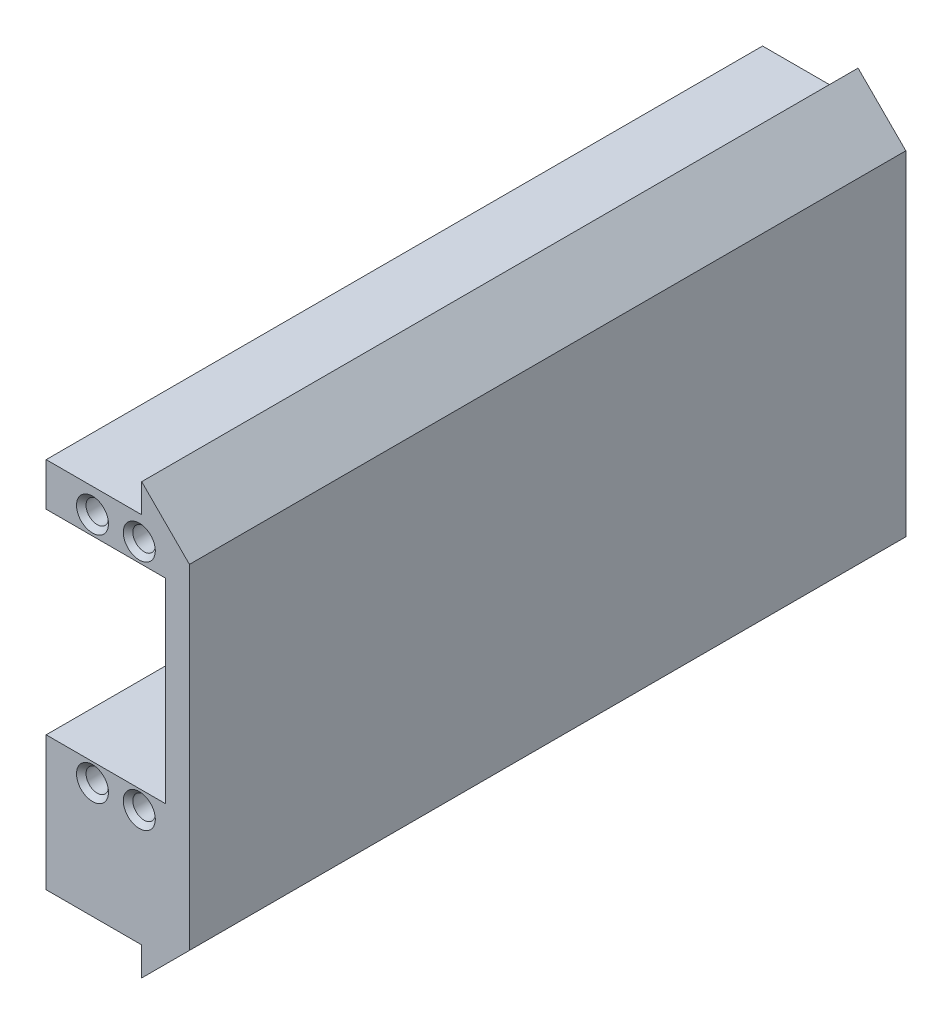
SolidWorks part; units mm, degrees
material "ABS"
ref_plane "Front Plane" through (0, 0, 0) normal (0, 0, 1) x (1, 0, 0)
ref_plane "Top Plane" through (0, 0, 0) normal (0, 1, 0) x (1, 0, 0)
ref_plane "Right Plane" through (0, 0, 0) normal (1, 0, 0) x (0, 0, -1)
sketch "Sketch1" plane through (0, 0, 0) normal (0, 0, 1) x (1, 0, 0)
  line L0 (-15, 45) -> (15, 45)
  line L1 (-15, 45) -> (15, 45) construction
  line L2 (-15, 45) -> (-15, -45) construction
  line L3 (-15, -45) -> (15, -45) construction
  line L4 (15, 45) -> (15, -45) construction
  line L5 (-15, 45) -> (15, -45) construction
  line L6 (-15, -45) -> (15, 45) construction
  line L7 (15, 45) -> (15, -45)
  line L8 (15, -45) -> (-15, -45)
  line L9 (-15, -45) -> (-15, -10.9)
  line L10 (-15, -10.9) -> (10, -10.9)
  line L11 (10, -10.9) -> (10, 30)
  line L12 (10, 30) -> (-15, 30)
  line L13 (-15, 30) -> (-15, 45)
  point P0 (0, 0)
  dimension "D1" = 90
  dimension "D2" = 30
  dimension "D3" = 40.9
  dimension "D4" = 15
  dimension "D5" = 5
extrude "Boss-Extrude1" add sketch "Sketch1" along normal blind 150
sketch "Sketch2" plane through (0, 0, 150) normal (0, 0, 1) x (1, 0, 0)
  line L0 (10, 30) -> (-10.8, 30) construction
  line L1 (-15, 30) -> (10, 30) construction
  line L2 (-0.4, 30) -> (-0.4, 33.89) construction
  line L3 (-0.4, 33.89) -> (4.5, 33.89) construction
  line L4 (10, 30) -> (10, -10.9) construction
  line L5 (10, 9.55) -> (15, 9.55) construction
  line L7 (15, -45) -> (15, 45) construction
  circle A0 centre (4.5, 33.89) radius 2.35
  circle A1 centre (-5.3, 33.89) radius 2.35
  circle A4 centre (4.5, -14.79) radius 2.35
  circle A5 centre (-5.3, -14.79) radius 2.35
  dimension "D4" = 4.7
  dimension "D1" = 20.8
  dimension "D2" = 3.89
  dimension "D3" = 4.9
extrude "Cut-Extrude1" cut sketch "Sketch2" against normal blind 8
sketch "Sketch3" plane through (0, 0, 0) normal (0, 0, -1) x (-1, 0, 0)
  line L0 (-10, 30) -> (10.8, 30) construction
  line L1 (15, 30) -> (-10, 30) construction
  line L2 (-10, 30) -> (-10, -10.9) construction
  line L3 (-10, 9.55) -> (-15, 9.55) construction
  line L5 (0.4, 30) -> (0.4, 33.89) construction
  line L6 (0.4, 33.89) -> (-4.5, 33.89) construction
  line L7 (-15, -45) -> (-15, 45) construction
  circle A0 centre (-4.5, 33.89) radius 2.35
  circle A1 centre (5.3, 33.89) radius 2.35
  circle A4 centre (-4.5, -14.79) radius 2.35
  circle A5 centre (5.3, -14.79) radius 2.35
  dimension "D4" = 4.7
  dimension "D1" = 20.8
  dimension "D2" = 3.89
  dimension "D3" = 4.9
extrude "Cut-Extrude2" cut sketch "Sketch3" against normal blind 8
chamfer "Chamfer1" distance 1 angle 45 8 edges at (2.15, 33.89, 0) (-2.95, 33.89, 0) (-7.65, 33.89, 150) (6.85, 33.89, 150) (2.15, -14.79, 150) (-2.95, -14.79, 150) (-7.65, -14.79, 0) (6.85, -14.79, 0)
sketch "Sketch4" plane through (0, 0, 150) normal (0, 0, 1) x (1, 0, 0)
  line L0 (0, 0) -> (15, 0) construction
  line L1 (-15, -45) -> (5, -45)
  line L2 (-15, -45) -> (-15, -39)
  line L3 (-15, -39) -> (5, -39)
  line L4 (5, -45) -> (5, -39)
  line L5 (15, -45) -> (15, 45) construction
  line L6 (-15, 39) -> (5, 39)
  line L7 (5, 45) -> (5, 39)
  line L8 (-15, 45) -> (5, 45)
  line L9 (-15, 45) -> (-15, 39)
  dimension "D1" = 6
  dimension "D2" = 20
extrude "Cut-Extrude3" cut sketch "Sketch4" against normal through all
chamfer "Chamfer2" distance 10 angle 45 2 edges at (15, -45, 75) (15, 45, 75)
